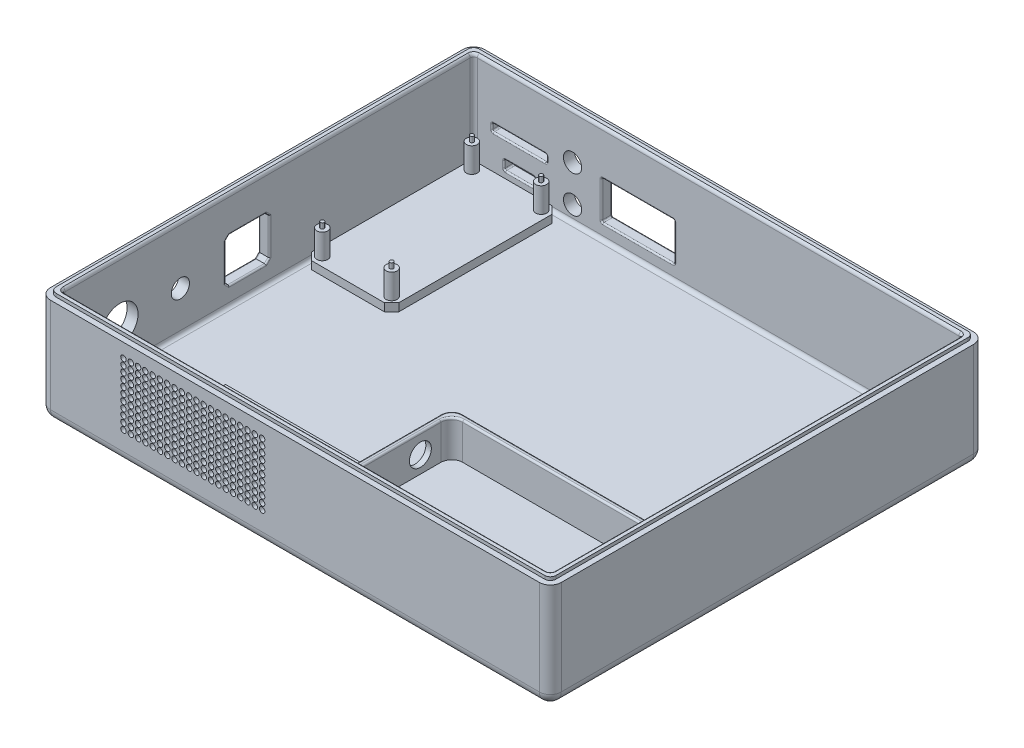
SolidWorks part; units mm, degrees
material "ABS"
ref_plane "Front Plane" through (0, 0, 0) normal (0, 0, 1) x (1, 0, 0)
ref_plane "Top Plane" through (0, 0, 0) normal (0, 1, 0) x (1, 0, 0)
ref_plane "Right Plane" through (0, 0, 0) normal (1, 0, 0) x (0, 0, -1)
sketch "Sketch1" plane through (0, 0, 0) normal (0, 1, 0) x (1, 0, 0)
  line L1 (-70, -59.5) -> (70, -59.5)
  line L2 (-70, -59.5) -> (-70, 59.5)
  line L3 (-70, 59.5) -> (70, 59.5)
  line L4 (70, -59.5) -> (70, 59.5)
  line L5 (-70, -59.5) -> (70, 59.5) construction
  line L6 (-70, 59.5) -> (70, -59.5) construction
  point P0 (0, 0)
  dimension "D1" = 140
  dimension "D2" = 119
extrude "Boss-Extrude1" add sketch "Sketch1" along normal blind 30
shell "Shell1" thickness 3 removed face at (0, 30, 0)
fillet "Fillet13" radius 1 12 edges at (-67, 30, 0) (67, 30, 0) (67, 16.5, 56.5) (0, 30, 56.5) (-67, 16.5, 56.5) (-67, 16.5, -56.5) (0, 30, -56.5) (67, 16.5, -56.5) (0, 3, 56.5) (-67, 3, 0) (0, 3, -56.5) (67, 3, 0)
fillet "Fillet2" radius 3 8 edges at (70, 0, 0) (0, 0, 59.5) (0, 0, -59.5) (-70, 0, 0) (70, 15, 59.5) (-70, 15, 59.5) (-70, 15, -59.5) (70, 15, -59.5)
sketch "Sketch4" plane through (0, 3, 0) normal (0, 1, 0) x (1, 0, 0)
  line L0 (-66, -55.5) -> (66, -55.5) construction
  line L1 (63, -54) -> (-2.5, -54)
  line L2 (63, -54) -> (63, -14)
  line L3 (63, -14) -> (-2.5, -14)
  line L4 (-2.5, -54) -> (-2.5, -14)
  line L5 (66, -55.5) -> (66, 55.5) construction
  dimension "D1" = 65.5
  dimension "D2" = 40
  dimension "D3" = 1.5
  dimension "D4" = 3
extrude "Boss-Extrude2" add sketch "Sketch4" along normal blind 10
sketch "Sketch5" plane through (0, 13, 0) normal (0, 1, 0) x (1, 0, 0)
  line L8 (61.5, -52.5) -> (61.5, -15.5)
  line L9 (61.5, -15.5) -> (-1, -15.5)
  line L10 (-1, -15.5) -> (-1, -52.5)
  line L11 (-1, -52.5) -> (61.5, -52.5)
  line L12 (61.5, -52.5) -> (61.5, -15.5)
  line L13 (61.5, -15.5) -> (-1, -15.5)
  line L14 (-1, -15.5) -> (-1, -52.5)
  line L15 (-1, -52.5) -> (61.5, -52.5)
  dimension "D1" = 1.5
extrude "Cut-Extrude1" cut sketch "Sketch5" against normal up to surface (10 mm away) up to face at (0, 3, 0)
sketch "Sketch19" plane through (0, 30, 0) normal (0, 1, 0) x (1, 0, 0)
  line L20 (70, -56.5) -> (70, 56.5) construction
  line L21 (-67, -59.5) -> (67, -59.5) construction
  line L22 (-70, 56.5) -> (-70, -56.5) construction
  line L23 (67, 59.5) -> (-67, 59.5) construction
  line L24 (68.5, -56.5) -> (68.5, 56.5)
  line L25 (-67, -58) -> (67, -58)
  line L26 (-68.5, 56.5) -> (-68.5, -56.5)
  line L27 (67, 58) -> (-67, 58)
  line L28 (68.5, -56.5) -> (68.5, 56.5)
  line L29 (-67, -58) -> (67, -58)
  line L30 (-68.5, 56.5) -> (-68.5, -56.5)
  line L31 (67, 58) -> (-67, 58)
  line L32 (70, -56.5) -> (70, 56.5)
  line L33 (-67, -59.5) -> (67, -59.5)
  line L34 (-70, 56.5) -> (-70, -56.5)
  line L35 (67, 59.5) -> (-67, 59.5)
  arc A16 (70, 56.5) -> (67, 59.5) centre (67, 56.5) ccw construction
  arc A17 (67, -59.5) -> (70, -56.5) centre (67, -56.5) ccw construction
  arc A18 (-70, -56.5) -> (-67, -59.5) centre (-67, -56.5) ccw construction
  arc A19 (-67, 59.5) -> (-70, 56.5) centre (-67, 56.5) ccw construction
  arc A20 (68.5, 56.5) -> (67, 58) centre (67, 56.5) ccw
  arc A21 (67, -58) -> (68.5, -56.5) centre (67, -56.5) ccw
  arc A22 (-68.5, -56.5) -> (-67, -58) centre (-67, -56.5) ccw
  arc A23 (-67, 58) -> (-68.5, 56.5) centre (-67, 56.5) ccw
  arc A24 (68.5, 56.5) -> (67, 58) centre (67, 56.5) ccw
  arc A25 (67, -58) -> (68.5, -56.5) centre (67, -56.5) ccw
  arc A26 (-68.5, -56.5) -> (-67, -58) centre (-67, -56.5) ccw
  arc A27 (-67, 58) -> (-68.5, 56.5) centre (-67, 56.5) ccw
  arc A28 (70, 56.5) -> (67, 59.5) centre (67, 56.5) ccw
  arc A29 (67, -59.5) -> (70, -56.5) centre (67, -56.5) ccw
  arc A30 (-70, -56.5) -> (-67, -59.5) centre (-67, -56.5) ccw
  arc A31 (-67, 59.5) -> (-70, 56.5) centre (-67, 56.5) ccw
  dimension "D1" = 1.5
extrude "Cut-Extrude13" cut sketch "Sketch19" against normal blind 1
sketch "Sketch20" plane through (0, 30, 0) normal (0, 1, 0) x (1, 0, 0)
  line L0 (67, -55.5) -> (67, 55.5) construction
  line L1 (-66, -56.5) -> (66, -56.5) construction
  line L2 (66, 56.5) -> (-66, 56.5) construction
  line L3 (-67, 55.5) -> (-67, -55.5) construction
  line L4 (67, 58) -> (-67, 58)
  line L5 (-68.5, 56.5) -> (-68.5, -56.5)
  line L6 (-67, -58) -> (67, -58)
  line L7 (68.5, -56.5) -> (68.5, 56.5)
  line L8 (67, 58) -> (-67, 58)
  line L9 (-68.5, 56.5) -> (-68.5, -56.5)
  line L10 (-67, -58) -> (67, -58)
  line L11 (68.5, -56.5) -> (68.5, 56.5)
  line L12 (67, -55.5) -> (67, 55.5)
  line L13 (-66, -56.5) -> (66, -56.5)
  line L14 (66, 56.5) -> (-66, 56.5)
  line L15 (-67, 55.5) -> (-67, -55.5)
  arc A0 (67, 55.5) -> (66, 56.5) centre (66, 55.5) ccw construction
  arc A1 (66, -56.5) -> (67, -55.5) centre (66, -55.5) ccw construction
  arc A2 (-67, -55.5) -> (-66, -56.5) centre (-66, -55.5) ccw construction
  arc A3 (-66, 56.5) -> (-67, 55.5) centre (-66, 55.5) ccw construction
  arc A4 (68.5, 56.5) -> (67, 58) centre (67, 56.5) ccw
  arc A5 (-67, 58) -> (-68.5, 56.5) centre (-67, 56.5) ccw
  arc A6 (-68.5, -56.5) -> (-67, -58) centre (-67, -56.5) ccw
  arc A7 (67, -58) -> (68.5, -56.5) centre (67, -56.5) ccw
  arc A8 (68.5, 56.5) -> (67, 58) centre (67, 56.5) ccw
  arc A9 (-67, 58) -> (-68.5, 56.5) centre (-67, 56.5) ccw
  arc A10 (-68.5, -56.5) -> (-67, -58) centre (-67, -56.5) ccw
  arc A11 (67, -58) -> (68.5, -56.5) centre (67, -56.5) ccw
  arc A12 (67, 55.5) -> (66, 56.5) centre (66, 55.5) ccw
  arc A13 (66, -56.5) -> (67, -55.5) centre (66, -55.5) ccw
  arc A14 (-67, -55.5) -> (-66, -56.5) centre (-66, -55.5) ccw
  arc A15 (-66, 56.5) -> (-67, 55.5) centre (-66, 55.5) ccw
  dimension "D1" = 0
extrude "Cut-Extrude14" cut sketch "Sketch20" against normal blind 0.1
sketch "Sketch22" plane through (0, 0, -59.5) normal (0, 0, -1) x (-1, 0, 0)
  line L0 (67, 3) -> (67, 29) construction
  line L1 (47, 15.55) -> (62, 15.55)
  line L2 (47, 15.55) -> (47, 13.55)
  line L3 (47, 13.55) -> (62, 13.55)
  line L4 (62, 15.55) -> (62, 13.55)
  line L5 (47, 15.55) -> (62, 13.55) construction
  line L6 (47, 13.55) -> (62, 15.55) construction
  line L7 (50.325, 8.55) -> (58.675, 8.55)
  line L8 (50.325, 8.55) -> (50.325, 6)
  line L9 (50.325, 6) -> (58.675, 6)
  line L10 (58.675, 8.55) -> (58.675, 6)
  line L11 (50.325, 8.55) -> (58.675, 6) construction
  line L12 (50.325, 6) -> (58.675, 8.55) construction
  line L13 (-67, 3) -> (67, 3) construction
  point P0 (54.5, 14.55)
  point P5 (54.5, 7.275)
  dimension "D1" = 5
  dimension "D2" = 8.35
  dimension "D3" = 2.55
  dimension "D4" = 3
  dimension "D5" = 15
  dimension "D6" = 2
  dimension "D7" = 5
extrude "Cut-Extrude15" cut sketch "Sketch22" against normal blind 60
sketch "Sketch24" plane through (0, 0, -59.5) normal (0, 0, -1) x (-1, 0, 0)
  line L0 (-67, 3) -> (67, 3) construction
  line L1 (12, 7) -> (32, 7)
  line L2 (12, 7) -> (12, 17.5)
  line L3 (12, 17.5) -> (32, 17.5)
  line L4 (32, 7) -> (32, 17.5)
  line L5 (12, 7) -> (32, 17.5) construction
  line L6 (12, 17.5) -> (32, 7) construction
  line L7 (67, 3) -> (67, 29) construction
  point P0 (22, 12.25)
  dimension "D1" = 20
  dimension "D2" = 10.5
  dimension "D3" = 4
  dimension "D4" = 35
extrude "Cut-Extrude16" cut sketch "Sketch24" against normal blind 60
sketch "Sketch25" plane through (0, 3, 0) normal (0, 1, 0) x (1, 0, 0)
  line L0 (-66, -55.5) -> (66, -55.5) construction
  line L1 (-46, -52.5) -> (-7, -52.5)
  line L2 (-46, -52.5) -> (-46, -32.5)
  line L3 (-46, -32.5) -> (-7, -32.5)
  line L4 (-7, -52.5) -> (-7, -32.5)
  line L5 (-46, -52.5) -> (-7, -32.5) construction
  line L6 (-46, -32.5) -> (-7, -52.5) construction
  line L7 (-66, 55.5) -> (-66, -55.5) construction
  point P0 (-26.5, -42.5)
  dimension "D1" = 20
  dimension "D2" = 39
  dimension "D3" = 3
  dimension "D4" = 20
sketch "Sketch26" plane through (0, 3, 0) normal (0, 1, 0) x (1, 0, 0)
  line L0 (-66, 56.5) -> (66, 56.5) construction
  line L1 (-64.5, 9.5) -> (-44.5, 9.5)
  line L2 (-66.5, 11.5) -> (-66.5, 53.5)
  line L3 (-64.5, 55.5) -> (-44.5, 55.5)
  line L4 (-42.5, 11.5) -> (-42.5, 53.5)
  line L5 (-66.5, 9.5) -> (-42.5, 55.5) construction
  line L6 (-66.5, 55.5) -> (-42.5, 9.5) construction
  line L9 (-44.5, 55.5) -> (-42.5, 53.5)
  line L10 (-66.5, 53.5) -> (-64.5, 55.5)
  line L11 (-66.5, 11.5) -> (-64.5, 9.5)
  line L12 (-44.5, 9.5) -> (-42.5, 11.5)
  point P0 (-54.5, 32.5)
  dimension "D1" = 24
  dimension "D2" = 46
  dimension "D3" = 1
  dimension "D4" = 4.5
sketch "Sketch27" plane through (0, 3, 0) normal (0, 1, 0) x (1, 0, 0)
  line L0 (-66.5, 53.5) -> (-64.5, 55.5) construction
  line L1 (-64.5, 55.5) -> (-44.5, 55.5) construction
  line L2 (-44.5, 55.5) -> (-42.5, 53.5) construction
  line L3 (-42.5, 11.5) -> (-42.5, 53.5) construction
  line L4 (-44.5, 9.5) -> (-42.5, 11.5) construction
  line L5 (-64.5, 9.5) -> (-44.5, 9.5) construction
  line L6 (-66.5, 11.5) -> (-64.5, 9.5) construction
  line L7 (-66.5, 11.5) -> (-66.5, 53.5) construction
  line L8 (-66.5, 55.5) -> (-42.5, 9.5) construction
  line L9 (-66.5, 9.5) -> (-42.5, 55.5) construction
  line L10 (-66.5, 53.5) -> (-64.5, 55.5)
  line L11 (-64.5, 55.5) -> (-44.5, 55.5)
  line L12 (-44.5, 55.5) -> (-42.5, 53.5)
  line L13 (-42.5, 11.5) -> (-42.5, 53.5)
  line L14 (-44.5, 9.5) -> (-42.5, 11.5)
  line L15 (-64.5, 9.5) -> (-44.5, 9.5)
  line L16 (-66.5, 11.5) -> (-64.5, 9.5)
  line L17 (-66.5, 11.5) -> (-66.5, 53.5)
  line L18 (-66.5, 55.5) -> (-42.5, 9.5) construction
  line L19 (-66.5, 9.5) -> (-42.5, 55.5) construction
extrude "Boss-Extrude3" add sketch "Sketch27" along normal blind 2.16
sketch "Sketch28" plane through (0, 5.16, 0) normal (0, 1, 0) x (1, 0, 0)
  line L3 (-64.5, 9.5) -> (-44.5, 9.5) construction
  line L4 (-66.5, 11.5) -> (-66.5, 53.5) construction
  line L5 (-66.5, 53.5) -> (-66.5, 11.5) construction
  line L6 (-44.5, 55.5) -> (-64.5, 55.5) construction
  line L7 (-42.5, 11.5) -> (-42.5, 53.5) construction
  line L8 (-64.5, 9.5) -> (-44.5, 9.5) construction
  circle A0 centre (-64, 53) radius 1.5
  circle A1 centre (-45, 53) radius 1.5
  circle A2 centre (-64, 12) radius 1.5
  circle A3 centre (-45, 12) radius 1.5
  dimension "D1" = 3
  dimension "D2" = 2.5
  dimension "D3" = 2.5
  dimension "D4" = 2.5
  dimension "D5" = 2.5
  dimension "D6" = 2.5
  dimension "D7" = 2.5
  dimension "D8" = 2.5
  dimension "D9" = 2.5
extrude "Boss-Extrude4" add sketch "Sketch28" along normal blind 6.8
sketch "Sketch29" plane through (0, 11.96, 0) normal (0, 1, 0) x (1, 0, 0)
  circle A12 centre (-64, 53) radius 0.5
  circle A15 centre (-64, 53) radius 0.5
  circle A21 centre (-45, 53) radius 0.5
  circle A22 centre (-45, 53) radius 0.5
  circle A24 centre (-64, 12) radius 0.5
  circle A25 centre (-64, 12) radius 0.5
  circle A27 centre (-45, 12) radius 0.5
  circle A28 centre (-45, 12) radius 0.5
  dimension "D4" = 1
  dimension "D3" = 1
  dimension "D1" = 1
  dimension "D2" = 1
extrude "Boss-Extrude5" add sketch "Sketch29" along normal blind 1.5
extrude "Boss-Extrude6" add sketch "Sketch25" along normal blind 3 contours L4 L3 L2 L1
sketch "Sketch31" plane through (-70, 0, 0) normal (-1, 0, 0) x (0, 0, 1)
  line L0 (-56.5, 3) -> (56.5, 3) construction
  line L1 (0.5, 8) -> (10.5, 8)
  line L2 (-0.5, 9) -> (-0.5, 19)
  line L3 (0.5, 20) -> (10.5, 20)
  line L4 (11.5, 9) -> (11.5, 19)
  line L5 (-0.5, 8) -> (11.5, 20) construction
  line L6 (-0.5, 20) -> (11.5, 8) construction
  line L7 (56.5, 3) -> (56.5, 29) construction
  line L8 (-0.5, 19) -> (0.5, 20)
  line L9 (10.5, 20) -> (11.5, 19)
  line L10 (-0.5, 9) -> (0.5, 8)
  line L11 (10.5, 8) -> (11.5, 9)
  point P0 (5.5, 14)
  dimension "D1" = 12
  dimension "D2" = 12
  dimension "D3" = 5
  dimension "D4" = 45
extrude "Cut-Extrude17" cut sketch "Sketch31" against normal blind 12
sketch "Sketch32" plane through (0, 0, 59.5) normal (0, 0, 1) x (1, 0, 0)
  line L0 (-67, 29) -> (-67, 3) construction
  line L1 (-48, 7) -> (-8, 7) construction
  line L2 (-48, 7) -> (-48, 26) construction
  line L3 (-48, 26) -> (-8, 26) construction
  line L4 (-8, 7) -> (-8, 26) construction
  line L5 (-48, 7) -> (-8, 26) construction
  line L6 (-48, 26) -> (-8, 7) construction
  line L7 (-67, 3) -> (67, 3) construction
  line L8 (-67, 29) -> (67, 29) construction
  circle A0 centre (-47, 25.2) radius 0.75
  circle A1 centre (-45, 25.2) radius 0.75
  circle A2 centre (-43, 25.2) radius 0.75
  circle A3 centre (-41, 25.2) radius 0.75
  circle A4 centre (-39, 25.2) radius 0.75
  circle A5 centre (-37, 25.2) radius 0.75
  circle A6 centre (-35, 25.2) radius 0.75
  circle A7 centre (-33, 25.2) radius 0.75
  circle A8 centre (-31, 25.2) radius 0.75
  circle A9 centre (-29, 25.2) radius 0.75
  circle A10 centre (-27, 25.2) radius 0.75
  circle A11 centre (-25, 25.2) radius 0.75
  circle A12 centre (-23, 25.2) radius 0.75
  circle A13 centre (-21, 25.2) radius 0.75
  circle A14 centre (-19, 25.2) radius 0.75
  circle A15 centre (-17, 25.2) radius 0.75
  circle A16 centre (-15, 25.2) radius 0.75
  circle A17 centre (-13, 25.2) radius 0.75
  circle A18 centre (-11, 25.2) radius 0.75
  circle A19 centre (-9, 25.2) radius 0.75
  circle A20 centre (-45, 23.5) radius 0.75
  circle A21 centre (-43, 23.5) radius 0.75
  circle A22 centre (-41, 23.5) radius 0.75
  circle A23 centre (-39, 23.5) radius 0.75
  circle A24 centre (-37, 23.5) radius 0.75
  circle A25 centre (-35, 23.5) radius 0.75
  circle A26 centre (-33, 23.5) radius 0.75
  circle A27 centre (-31, 23.5) radius 0.75
  circle A28 centre (-29, 23.5) radius 0.75
  circle A29 centre (-27, 23.5) radius 0.75
  circle A30 centre (-25, 23.5) radius 0.75
  circle A31 centre (-23, 23.5) radius 0.75
  circle A32 centre (-21, 23.5) radius 0.75
  circle A33 centre (-19, 23.5) radius 0.75
  circle A34 centre (-17, 23.5) radius 0.75
  circle A35 centre (-15, 23.5) radius 0.75
  circle A36 centre (-13, 23.5) radius 0.75
  circle A37 centre (-11, 23.5) radius 0.75
  circle A38 centre (-9, 23.5) radius 0.75
  circle A39 centre (-45, 21.8) radius 0.75
  circle A40 centre (-43, 21.8) radius 0.75
  circle A41 centre (-41, 21.8) radius 0.75
  circle A42 centre (-39, 21.8) radius 0.75
  circle A43 centre (-37, 21.8) radius 0.75
  circle A44 centre (-35, 21.8) radius 0.75
  circle A45 centre (-33, 21.8) radius 0.75
  circle A46 centre (-31, 21.8) radius 0.75
  circle A47 centre (-29, 21.8) radius 0.75
  circle A48 centre (-27, 21.8) radius 0.75
  circle A49 centre (-25, 21.8) radius 0.75
  circle A50 centre (-23, 21.8) radius 0.75
  circle A51 centre (-21, 21.8) radius 0.75
  circle A52 centre (-19, 21.8) radius 0.75
  circle A53 centre (-17, 21.8) radius 0.75
  circle A54 centre (-15, 21.8) radius 0.75
  circle A55 centre (-13, 21.8) radius 0.75
  circle A56 centre (-11, 21.8) radius 0.75
  circle A57 centre (-9, 21.8) radius 0.75
  circle A58 centre (-45, 20.1) radius 0.75
  circle A59 centre (-43, 20.1) radius 0.75
  circle A60 centre (-41, 20.1) radius 0.75
  circle A61 centre (-39, 20.1) radius 0.75
  circle A62 centre (-37, 20.1) radius 0.75
  circle A63 centre (-35, 20.1) radius 0.75
  circle A64 centre (-33, 20.1) radius 0.75
  circle A65 centre (-31, 20.1) radius 0.75
  circle A66 centre (-29, 20.1) radius 0.75
  circle A67 centre (-27, 20.1) radius 0.75
  circle A68 centre (-25, 20.1) radius 0.75
  circle A69 centre (-23, 20.1) radius 0.75
  circle A70 centre (-21, 20.1) radius 0.75
  circle A71 centre (-19, 20.1) radius 0.75
  circle A72 centre (-17, 20.1) radius 0.75
  circle A73 centre (-15, 20.1) radius 0.75
  circle A74 centre (-13, 20.1) radius 0.75
  circle A75 centre (-11, 20.1) radius 0.75
  circle A76 centre (-9, 20.1) radius 0.75
  circle A77 centre (-45, 18.4) radius 0.75
  circle A78 centre (-43, 18.4) radius 0.75
  circle A79 centre (-41, 18.4) radius 0.75
  circle A80 centre (-39, 18.4) radius 0.75
  circle A81 centre (-37, 18.4) radius 0.75
  circle A82 centre (-35, 18.4) radius 0.75
  circle A83 centre (-33, 18.4) radius 0.75
  circle A84 centre (-31, 18.4) radius 0.75
  circle A85 centre (-29, 18.4) radius 0.75
  circle A86 centre (-27, 18.4) radius 0.75
  circle A87 centre (-25, 18.4) radius 0.75
  circle A88 centre (-23, 18.4) radius 0.75
  circle A89 centre (-21, 18.4) radius 0.75
  circle A90 centre (-19, 18.4) radius 0.75
  circle A91 centre (-17, 18.4) radius 0.75
  circle A92 centre (-15, 18.4) radius 0.75
  circle A93 centre (-13, 18.4) radius 0.75
  circle A94 centre (-11, 18.4) radius 0.75
  circle A95 centre (-9, 18.4) radius 0.75
  circle A96 centre (-45, 16.7) radius 0.75
  circle A97 centre (-43, 16.7) radius 0.75
  circle A98 centre (-41, 16.7) radius 0.75
  circle A99 centre (-39, 16.7) radius 0.75
  circle A100 centre (-37, 16.7) radius 0.75
  circle A101 centre (-35, 16.7) radius 0.75
  circle A102 centre (-33, 16.7) radius 0.75
  circle A103 centre (-31, 16.7) radius 0.75
  circle A104 centre (-29, 16.7) radius 0.75
  circle A105 centre (-27, 16.7) radius 0.75
  circle A106 centre (-25, 16.7) radius 0.75
  circle A107 centre (-23, 16.7) radius 0.75
  circle A108 centre (-21, 16.7) radius 0.75
  circle A109 centre (-19, 16.7) radius 0.75
  circle A110 centre (-17, 16.7) radius 0.75
  circle A111 centre (-15, 16.7) radius 0.75
  circle A112 centre (-13, 16.7) radius 0.75
  circle A113 centre (-11, 16.7) radius 0.75
  circle A114 centre (-9, 16.7) radius 0.75
  circle A115 centre (-45, 15) radius 0.75
  circle A116 centre (-43, 15) radius 0.75
  circle A117 centre (-41, 15) radius 0.75
  circle A118 centre (-39, 15) radius 0.75
  circle A119 centre (-37, 15) radius 0.75
  circle A120 centre (-35, 15) radius 0.75
  circle A121 centre (-33, 15) radius 0.75
  circle A122 centre (-31, 15) radius 0.75
  circle A123 centre (-29, 15) radius 0.75
  circle A124 centre (-27, 15) radius 0.75
  circle A125 centre (-25, 15) radius 0.75
  circle A126 centre (-23, 15) radius 0.75
  circle A127 centre (-21, 15) radius 0.75
  circle A128 centre (-19, 15) radius 0.75
  circle A129 centre (-17, 15) radius 0.75
  circle A130 centre (-15, 15) radius 0.75
  circle A131 centre (-13, 15) radius 0.75
  circle A132 centre (-11, 15) radius 0.75
  circle A133 centre (-9, 15) radius 0.75
  circle A134 centre (-45, 13.3) radius 0.75
  circle A135 centre (-43, 13.3) radius 0.75
  circle A136 centre (-41, 13.3) radius 0.75
  circle A137 centre (-39, 13.3) radius 0.75
  circle A138 centre (-37, 13.3) radius 0.75
  circle A139 centre (-35, 13.3) radius 0.75
  circle A140 centre (-33, 13.3) radius 0.75
  circle A141 centre (-31, 13.3) radius 0.75
  circle A142 centre (-29, 13.3) radius 0.75
  circle A143 centre (-27, 13.3) radius 0.75
  circle A144 centre (-25, 13.3) radius 0.75
  circle A145 centre (-23, 13.3) radius 0.75
  circle A146 centre (-21, 13.3) radius 0.75
  circle A147 centre (-19, 13.3) radius 0.75
  circle A148 centre (-17, 13.3) radius 0.75
  circle A149 centre (-15, 13.3) radius 0.75
  circle A150 centre (-13, 13.3) radius 0.75
  circle A151 centre (-11, 13.3) radius 0.75
  circle A152 centre (-9, 13.3) radius 0.75
  circle A153 centre (-45, 11.6) radius 0.75
  circle A154 centre (-43, 11.6) radius 0.75
  circle A155 centre (-41, 11.6) radius 0.75
  circle A156 centre (-39, 11.6) radius 0.75
  circle A157 centre (-37, 11.6) radius 0.75
  circle A158 centre (-35, 11.6) radius 0.75
  circle A159 centre (-33, 11.6) radius 0.75
  circle A160 centre (-31, 11.6) radius 0.75
  circle A161 centre (-29, 11.6) radius 0.75
  circle A162 centre (-27, 11.6) radius 0.75
  circle A163 centre (-25, 11.6) radius 0.75
  circle A164 centre (-23, 11.6) radius 0.75
  circle A165 centre (-21, 11.6) radius 0.75
  circle A166 centre (-19, 11.6) radius 0.75
  circle A167 centre (-17, 11.6) radius 0.75
  circle A168 centre (-15, 11.6) radius 0.75
  circle A169 centre (-13, 11.6) radius 0.75
  circle A170 centre (-11, 11.6) radius 0.75
  circle A171 centre (-9, 11.6) radius 0.75
  circle A172 centre (-45, 9.9) radius 0.75
  circle A173 centre (-43, 9.9) radius 0.75
  circle A174 centre (-41, 9.9) radius 0.75
  circle A175 centre (-39, 9.9) radius 0.75
  circle A176 centre (-37, 9.9) radius 0.75
  circle A177 centre (-35, 9.9) radius 0.75
  circle A178 centre (-33, 9.9) radius 0.75
  circle A179 centre (-31, 9.9) radius 0.75
  circle A180 centre (-29, 9.9) radius 0.75
  circle A181 centre (-27, 9.9) radius 0.75
  circle A182 centre (-25, 9.9) radius 0.75
  circle A183 centre (-23, 9.9) radius 0.75
  circle A184 centre (-21, 9.9) radius 0.75
  circle A185 centre (-19, 9.9) radius 0.75
  circle A186 centre (-17, 9.9) radius 0.75
  circle A187 centre (-15, 9.9) radius 0.75
  circle A188 centre (-13, 9.9) radius 0.75
  circle A189 centre (-11, 9.9) radius 0.75
  circle A190 centre (-9, 9.9) radius 0.75
  circle A191 centre (-45, 8.2) radius 0.75
  circle A192 centre (-43, 8.2) radius 0.75
  circle A193 centre (-41, 8.2) radius 0.75
  circle A194 centre (-39, 8.2) radius 0.75
  circle A195 centre (-37, 8.2) radius 0.75
  circle A196 centre (-35, 8.2) radius 0.75
  circle A197 centre (-33, 8.2) radius 0.75
  circle A198 centre (-31, 8.2) radius 0.75
  circle A199 centre (-29, 8.2) radius 0.75
  circle A200 centre (-27, 8.2) radius 0.75
  circle A201 centre (-25, 8.2) radius 0.75
  circle A202 centre (-23, 8.2) radius 0.75
  circle A203 centre (-21, 8.2) radius 0.75
  circle A204 centre (-19, 8.2) radius 0.75
  circle A205 centre (-17, 8.2) radius 0.75
  circle A206 centre (-15, 8.2) radius 0.75
  circle A207 centre (-13, 8.2) radius 0.75
  circle A208 centre (-11, 8.2) radius 0.75
  circle A209 centre (-9, 8.2) radius 0.75
  circle A210 centre (-47, 23.5) radius 0.75
  circle A211 centre (-47, 21.8) radius 0.75
  circle A212 centre (-47, 20.1) radius 0.75
  circle A213 centre (-47, 18.4) radius 0.75
  circle A214 centre (-47, 16.7) radius 0.75
  circle A215 centre (-47, 15) radius 0.75
  circle A216 centre (-47, 13.3) radius 0.75
  circle A217 centre (-47, 11.6) radius 0.75
  circle A218 centre (-47, 9.9) radius 0.75
  circle A219 centre (-47, 8.2) radius 0.75
  point P0 (-28, 16.5)
  dimension "D5" = 1.5
  dimension "D1" = 19
  dimension "D2" = 4
  dimension "D3" = 3
  dimension "D4" = 40
  dimension "D6" = 1
  dimension "D7" = 0.8
  dimension "D8" = 20
  dimension "D9" = 11
extrude "Cut-Extrude19" cut sketch "Sketch32" against normal blind 6
fillet "Fillet14" radius 0.4 16 edges at (-70, 8.5, 0) (-70, 8, 5.5) (-70, 8.5, 11) (-70, 14, 11.5) (-70, 19.5, 11) (-70, 20, 5.5) (-70, 19.5, 0) (-70, 14, -0.5) (-67, 20, 5.5) (-67, 19.5, 11) (-67, 14, 11.5) (-67, 8.5, 11) (-67, 8, 5.5) (-67, 8.5, 0) (-67, 19.5, 0) (-67, 14, -0.5)
fillet "Fillet15" radius 0.4 12 edges at (-22, 17.5, -56.5) (-22, 17.5, -59.5) (-22, 7, -59.5) (-22, 7, -56.5) (-12, 7, -58) (-12, 12.25, -59.5) (-12, 17.5, -58) (-12, 12.25, -56.5) (-32, 17.5, -58) (-32, 12.25, -59.5) (-32, 7, -58) (-32, 12.25, -56.5)
fillet "Fillet16" radius 0.4 24 edges at (-58.675, 7.275, -56.5) (-58.675, 7.275, -59.5) (-50.325, 7.275, -59.5) (-50.325, 7.275, -56.5) (-62, 14.55, -56.5) (-62, 14.55, -59.5) (-47, 14.55, -59.5) (-47, 14.55, -56.5) (-50.325, 8.55, -58) (-54.5, 8.55, -59.5) (-58.675, 8.55, -58) (-54.5, 8.55, -56.5) (-58.675, 6, -58) (-54.5, 6, -59.5) (-50.325, 6, -58) (-54.5, 6, -56.5) (-47, 15.55, -58) (-54.5, 15.55, -59.5) (-62, 15.55, -58) (-54.5, 15.55, -56.5) (-62, 13.55, -58) (-54.5, 13.55, -59.5) (-47, 13.55, -58) (-54.5, 13.55, -56.5)
sketch "Sketch42" plane through (-67, 0, 0) normal (1, 0, 0) x (0, 0, -1)
  line L0 (-56.5, 3) -> (-56.5, 29) construction
  circle A0 centre (-40.5, 13.7347) radius 5
  dimension "D1" = 10
  dimension "D2" = 16
extrude "Cut-Extrude24" cut sketch "Sketch42" against normal blind 12
sketch "Sketch43" plane through (-67, 0, 0) normal (1, 0, 0) x (0, 0, -1)
  line L0 (0.9, 8.8343) -> (0.9, 19.1657) construction
  line L1 (-11.9, 19.1657) -> (-11.9, 8.8343) construction
  circle A0 centre (-23.9, 14) radius 2.5
  point P8 (0.9, 14)
  dimension "D1" = 5
  dimension "D2" = 12
extrude "Cut-Extrude25" cut sketch "Sketch43" against normal blind 12
sketch "Sketch44" plane through (-2.5, 0, 0) normal (-1, 0, 0) x (0, 0, 1)
  circle A0 centre (24.1133, 7.6206) radius 3
  point P2 (24.1133, 7.6206)
  dimension "D1" = 6
extrude "Cut-Extrude26" cut sketch "Sketch44" against normal blind 12
fillet "Fillet18" radius 3 8 edges at (61.5, 8, 52.5) (61.5, 8, 15.5) (-1, 8, 52.5) (-1, 8, 15.5) (-2.5, 8, 14) (-2.5, 8, 54) (63, 8, 54) (63, 8, 14)
sketch "Sketch45" plane through (0, 0, -59.5) normal (0, 0, -1) x (-1, 0, 0)
  line L0 (39.9, 17.25) -> (39.9, 7.25) construction
  line L1 (32.4, 12.25) -> (39.9, 12.25) construction
  line L2 (32.4, 17.1) -> (32.4, 7.4) construction
  circle A0 centre (39.9, 17.25) radius 2.5
  circle A1 centre (39.9, 7.25) radius 2.5
  point P8 (39.9, 12.25)
  dimension "D1" = 5
  dimension "D2" = 10
  dimension "D3" = 7.5
extrude "Cut-Extrude27" cut sketch "Sketch45" against normal blind 12
fillet "Fillet19" radius 0.5 16 edges at (-0.1213, 13, 16.3787) (30.25, 13, 15.5) (60.6213, 13, 16.3787) (61.5, 13, 34) (60.6213, 13, 51.6213) (30.25, 13, 52.5) (-0.1213, 13, 51.6213) (30.25, 13, 14) (62.1213, 13, 14.8787) (63, 13, 34) (62.1213, 13, 53.1213) (30.25, 13, 54) (-1.6213, 13, 53.1213) (-2.5, 13, 34) (-1, 13, 34) (-1.6213, 13, 14.8787)
sketch "Sketch48" plane through (0, 0, 0) normal (0, 0, 1) x (1, 0, 0)
  line L0 (0, 0) -> (0, 29.9) construction
  line L1 (67, 0) -> (-67, 0) construction
  line L2 (-67, 29.9) -> (67, 29.9) construction
  line L3 (-20, 0) -> (-20, -6)
  line L4 (-20, -6) -> (20, -6)
  line L5 (20, -6) -> (20, 0)
  line L6 (-24, 0) -> (-24, -10)
  line L7 (-24, -10) -> (24, -10)
  line L8 (24, -10) -> (24, 0)
  line L9 (-24, 0) -> (-20, 0)
  line L10 (20, 0) -> (24, 0)
  point P10 (0, -6)
  dimension "D1" = 40
  dimension "D2" = 6
  dimension "D3" = 4
extrude "Boss-Extrude10" add sketch "Sketch48" along normal mid plane 12
fillet "Fillet20" radius 0.5 16 edges at (-24, -5, -6) (0, -10, -6) (24, -5, -6) (20, -3, -6) (0, -6, -6) (-20, -3, -6) (24, -5, 6) (20, -3, 6) (0, -6, 6) (-20, -3, 6) (-20, -6, 0) (20, -6, 0) (24, -10, 0) (-24, -10, 0) (0, -10, 6) (-24, -5, 6)
fillet "Fillet21" radius 0.5 16 edges at (23.8536, 0, -5.8536) (24, 0, 0) (23.8536, 0, 5.8536) (22, 0, 6) (20.1464, 0, 5.8536) (20, 0, 0) (20.1464, 0, -5.8536) (-23.8536, 0, 5.8536) (-22, 0, 6) (-20.1464, 0, 5.8536) (-20, 0, 0) (-20.1464, 0, -5.8536) (-22, 0, -6) (-23.8536, 0, -5.8536) (22, 0, -6) (-24, 0, 0)
